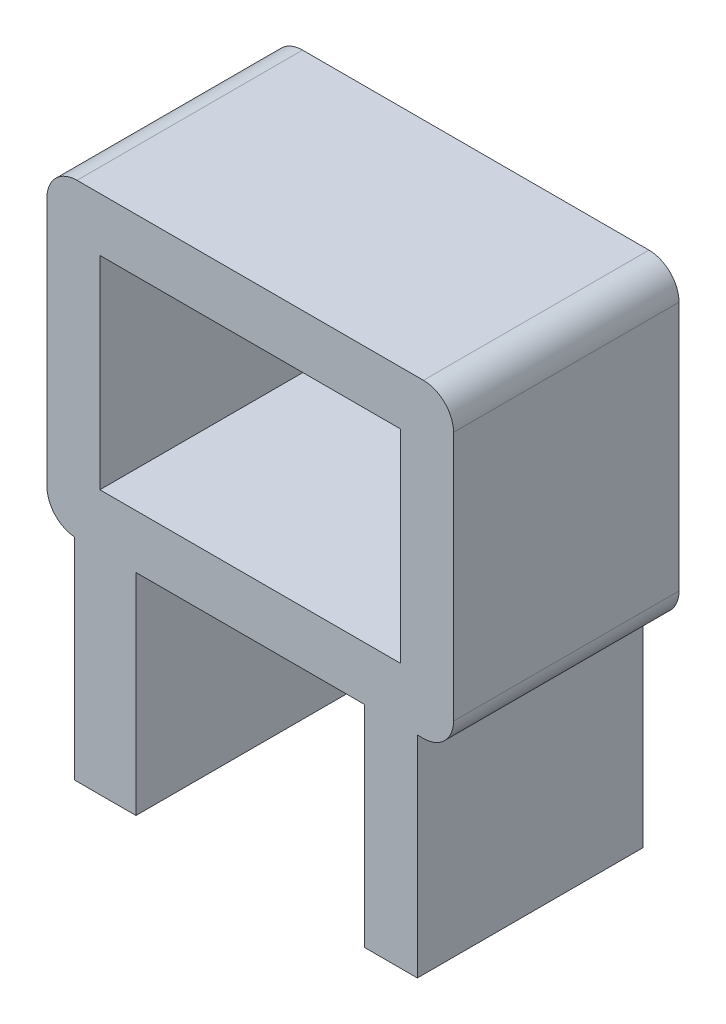
SolidWorks part; units mm, degrees
ref_plane "Front Plane" through (0, 0, 0) normal (0, 0, 1) x (1, 0, 0)
ref_plane "Top Plane" through (0, 0, 0) normal (0, 1, 0) x (1, 0, 0)
ref_plane "Right Plane" through (0, 0, 0) normal (1, 0, 0) x (0, 0, -1)
sketch "Sketch1" plane through (0, 0, 0) normal (0, 0, 1) x (1, 0, 0)
  line L0 (-12.3047, -0.6942) -> (-12.3047, -14.6942) construction
  line L1 (-22.3047, 16.3705) -> (-2.3047, 16.3705)
  line L2 (-22.3047, 16.3705) -> (-22.3047, 2.8705)
  line L3 (-22.3047, 2.8705) -> (-2.3047, 2.8705)
  line L4 (-2.3047, 16.3705) -> (-2.3047, 2.8705)
  line L5 (-22.3047, 16.3705) -> (-2.3047, 2.8705) construction
  line L6 (-22.3047, 2.8705) -> (-2.3047, 16.3705) construction
  line L7 (-25.8251, 19.9351) -> (1.2157, 19.9351)
  line L8 (-25.8251, 19.9351) -> (-25.8251, -0.6942)
  line L9 (-25.8251, -0.6942) -> (-24.0068, -0.6942)
  line L10 (1.2157, 19.9351) -> (1.2157, -0.6942)
  line L11 (-25.8251, 19.9351) -> (1.2157, -0.6942) construction
  line L12 (-25.8251, -0.6942) -> (1.2157, 19.9351) construction
  line L13 (-12.3047, -14.6942) -> (3.4918, -14.6942) construction
  line L14 (3.4918, -14.6942) -> (-27.1051, -14.6942) construction
  line L15 (-19.9047, -0.6942) -> (-19.9047, -28.1413) construction
  line L16 (-4.7047, -0.6942) -> (-4.7047, -28.7741) construction
  line L17 (-19.9047, -0.6942) -> (-19.9047, -14.6942)
  line L18 (-19.9047, -14.6942) -> (-24.0068, -14.6942)
  line L19 (-24.0068, -14.6942) -> (-24.0068, -0.6942)
  line L20 (-4.7047, -0.6942) -> (-4.7047, -14.6942)
  line L21 (-4.7047, -14.6942) -> (-1.5428, -14.6942)
  line L22 (-1.1881, -14.6942) -> (-1.1881, -0.6942)
  line L23 (-19.9047, -0.6942) -> (-4.7047, -0.6942)
  line L24 (-1.1881, -0.6942) -> (1.2157, -0.6942)
  line L25 (-1.5428, -14.6942) -> (-1.1881, -14.6942)
  point P0 (-12.3047, 9.6205)
  point P6 (-12.3047, 9.6205)
  dimension "D1" = 7.6
  dimension "D2" = 7.6
  dimension "D3" = 13.5
  dimension "D4" = 20
  dimension "D5" = 14
extrude "Boss-Extrude1" add sketch "Sketch1" along normal blind 15
fillet "Fillet1" radius 2 4 edges at (-25.8251, -0.6942, 7.5) (1.2157, -0.6942, 7.5) (-25.8251, 19.9351, 7.5) (1.2157, 19.9351, 7.5)
